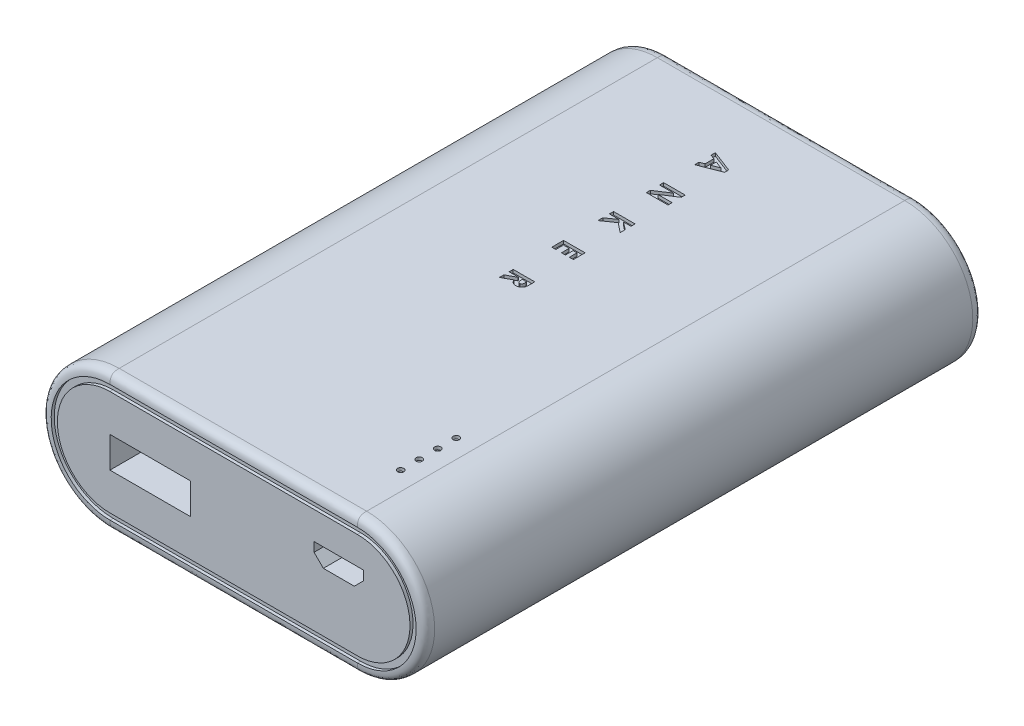
SolidWorks part; units mm, degrees
ref_plane "Front Plane" through (0, 0, 0) normal (0, 0, 1) x (1, 0, 0)
ref_plane "Top Plane" through (0, 0, 0) normal (0, 1, 0) x (1, 0, 0)
ref_plane "Right Plane" through (0, 0, 0) normal (1, 0, 0) x (0, 0, -1)
sketch "Sketch1" plane through (0, 0, 0) normal (0, 0, 1) x (1, 0, 0)
  line L0 (-34.7795, 0) -> (27.2205, 0) construction
  line L1 (-3.7795, 11) -> (-3.7795, -11) construction
  line L2 (-23.7795, 11) -> (16.2205, 11)
  line L3 (-23.7795, -11) -> (16.2205, -11)
  circle A0 centre (-23.7795, 0) radius 11 construction
  circle A1 centre (16.2205, 0) radius 11 construction
  arc A2 (-23.7795, 11) -> (-23.7795, -11) centre (-23.7795, 0) ccw
  arc A3 (16.2205, -11) -> (16.2205, 11) centre (16.2205, 0) ccw
  dimension "D3" = 22
  dimension "D4" = 22
  dimension "D1" = 62
  dimension "D2" = 22
  dimension "D5" = 20
extrude "Boss-Extrude2" add sketch "Sketch1" along normal blind 90 contours L2 A3 L3 A2
sketch "Sketch2" plane through (0, 0, 90) normal (0, 0, 1) x (1, 0, 0)
  line L1 (-23.7795, 2.5) -> (-10.7795, 2.5)
  line L2 (-23.7795, 2.5) -> (-23.7795, -2.5)
  line L3 (-23.7795, -2.5) -> (-10.7795, -2.5)
  line L4 (-10.7795, 2.5) -> (-10.7795, -2.5)
  dimension "D1" = 13
  dimension "D2" = 5
  dimension "D3" = 2.5
  dimension "D4" = 11
extrude "Cut-Extrude1" cut sketch "Sketch2" against normal blind 10
sketch "Sketch3" plane through (0, 0, 90) normal (0, 0, 1) x (1, 0, 0)
  line L0 (9.2205, 4) -> (17.2205, 4)
  line L1 (17.2205, 4) -> (17.2205, 2.5)
  line L2 (17.2205, 2.5) -> (15.7205, 1)
  line L3 (15.7205, 1) -> (10.7205, 1)
  line L4 (10.7205, 1) -> (9.2205, 2.5)
  line L5 (9.2205, 2.5) -> (9.2205, 4)
  point P2 (15.1383, 1.0626)
  point P7 (0, 0)
  dimension "D1" = 8
  dimension "D2" = 5
  dimension "D3" = 3
  dimension "D4" = 1.5
  dimension "D5" = 1.5
  dimension "D6" = 1
  dimension "D7" = 10
extrude "Cut-Extrude2" cut sketch "Sketch3" against normal blind 5
fillet "Fillet1" radius 1.5 4 edges at (-34.7795, 0, 90) (-3.7795, -11, 90) (27.2205, 0, 90) (-3.7795, 11, 90) curvature continuous yes
sketch "Sketch4" plane through (0, 0, 90) normal (0, 0, 1) x (1, 0, 0)
  line L4 (-23.7795, -8.5) -> (16.2205, -8.5)
  line L5 (16.2205, 8.5) -> (-23.7795, 8.5)
  line L6 (-23.7795, -8.5) -> (16.2205, -8.5)
  line L7 (16.2205, 8.5) -> (-23.7795, 8.5)
  line L12 (-23.7795, -9.5) -> (16.2205, -9.5)
  line L13 (16.2205, 9.5) -> (-23.7795, 9.5)
  line L14 (-23.7795, -9.5) -> (16.2205, -9.5)
  line L15 (16.2205, 9.5) -> (-23.7795, 9.5)
  spline S4 degree 3 poles (343.2267, -3971.8149) (-612.7811, 2316.078) (-95.2895, -30.8151) (18.148, -8.285) (18.4171, -8.2175) (18.9506, -8.055) (19.2157, -7.9596) (19.9879, -7.6399) (20.477, -7.3805) (21.4009, -6.764) (21.8375, -6.4036) (22.6224, -5.6191) (22.9758, -5.1922) (23.4421, -4.4952) (23.5867, -4.2533) (23.8484, -3.7618) (23.9665, -3.5108) (24.1787, -2.999) (24.2728, -2.7382) (24.4354, -2.2062) (24.5042, -1.9336) (24.6681, -1.1098) (24.7202, -0.5578) (24.7206, 0.274) (24.7077, 0.5519) (24.6539, 1.1091) (24.613, 1.3872) (24.4501, 2.2051) (24.2878, 2.7344) (23.9688, 3.5059) (23.8491, 3.7606) (23.5866, 4.2537) (23.444, 4.492) (22.9826, 5.1827) (22.6302, 5.6106) (21.8384, 6.4034) (21.4088, 6.7578) (20.719, 7.2194) (20.4812, 7.362) (19.9897, 7.6243) (19.7349, 7.7444) (18.9622, 8.065) (18.4329, 8.2277) (-15.4752, 15.0123) (-115.9896, -182.7222) (3962.0184, -608.1779) knots -12.967802 -12.967802 -12.967802 -12.967802 0.0625 0.0625 0.09375 0.09375 0.125 0.125 0.1875 0.1875 0.25 0.25 0.3125 0.3125 0.34375 0.34375 0.375 0.375 0.40625 0.40625 0.4375 0.4375 0.5 0.5 0.53125 0.53125 0.5625 0.5625 0.625 0.625 0.65625 0.65625 0.6875 0.6875 0.75 0.75 0.8125 0.8125 0.84375 0.84375 0.875 0.875 0.9375 0.9375 4.768553 4.768553 4.768553 4.768553 only from (16.2205, -8.5) to (16.2205, 8.5)
  spline S5 degree 3 poles (-350.7857, 3971.8149) (605.2221, -2316.078) (87.7305, 30.8151) (-25.707, 8.285) (-25.9761, 8.2175) (-26.5096, 8.055) (-26.7747, 7.9596) (-27.5469, 7.6399) (-28.036, 7.3805) (-28.9599, 6.764) (-29.3965, 6.4036) (-30.1814, 5.6191) (-30.5348, 5.1922) (-31.0011, 4.4952) (-31.1457, 4.2533) (-31.4074, 3.7618) (-31.5255, 3.5108) (-31.7377, 2.999) (-31.8318, 2.7382) (-31.9944, 2.2062) (-32.0632, 1.9336) (-32.2271, 1.1098) (-32.2793, 0.5578) (-32.2796, -0.274) (-32.2668, -0.5519) (-32.213, -1.1091) (-32.172, -1.3872) (-32.0091, -2.2051) (-31.8469, -2.7344) (-31.5278, -3.5059) (-31.4081, -3.7606) (-31.1456, -4.2537) (-31.003, -4.492) (-30.5417, -5.1827) (-30.1892, -5.6106) (-29.3975, -6.4034) (-28.9678, -6.7578) (-28.278, -7.2194) (-28.0402, -7.362) (-27.5488, -7.6243) (-27.2939, -7.7444) (-26.5212, -8.065) (-25.9919, -8.2277) (7.9161, -15.0123) (108.4306, 182.7222) (-3969.5774, 608.1779) knots -12.967802 -12.967802 -12.967802 -12.967802 0.0625 0.0625 0.09375 0.09375 0.125 0.125 0.1875 0.1875 0.25 0.25 0.3125 0.3125 0.34375 0.34375 0.375 0.375 0.40625 0.40625 0.4375 0.4375 0.5 0.5 0.53125 0.53125 0.5625 0.5625 0.625 0.625 0.65625 0.65625 0.6875 0.6875 0.75 0.75 0.8125 0.8125 0.84375 0.84375 0.875 0.875 0.9375 0.9375 4.768553 4.768553 4.768553 4.768553 only from (-23.7795, 8.5) to (-23.7795, -8.5)
  spline S6 degree 3 poles (16.2205, -8.5) (16.7817, -8.5) (17.3338, -8.4467) (18.148, -8.285) (18.4171, -8.2175) (18.9506, -8.055) (19.2157, -7.9596) (19.9879, -7.6399) (20.477, -7.3805) (21.4009, -6.764) (21.8375, -6.4036) (22.6224, -5.6191) (22.9758, -5.1922) (23.4421, -4.4952) (23.5867, -4.2533) (23.8484, -3.7618) (23.9665, -3.5108) (24.1787, -2.999) (24.2728, -2.7382) (24.4354, -2.2062) (24.5042, -1.9336) (24.6681, -1.1098) (24.7202, -0.5578) (24.7206, 0.274) (24.7077, 0.5519) (24.6539, 1.1091) (24.613, 1.3872) (24.4501, 2.2051) (24.2878, 2.7344) (23.9688, 3.5059) (23.8491, 3.7606) (23.5866, 4.2537) (23.444, 4.492) (22.9826, 5.1827) (22.6302, 5.6106) (21.8384, 6.4034) (21.4088, 6.7578) (20.719, 7.2194) (20.4812, 7.362) (19.9897, 7.6243) (19.7349, 7.7444) (18.9622, 8.065) (18.4329, 8.2277) (17.3443, 8.4455) (16.7821, 8.5) (16.2205, 8.5) knots 0 0 0 0 0.0625 0.0625 0.09375 0.09375 0.125 0.125 0.1875 0.1875 0.25 0.25 0.3125 0.3125 0.34375 0.34375 0.375 0.375 0.40625 0.40625 0.4375 0.4375 0.5 0.5 0.53125 0.53125 0.5625 0.5625 0.625 0.625 0.65625 0.65625 0.6875 0.6875 0.75 0.75 0.8125 0.8125 0.84375 0.84375 0.875 0.875 0.9375 0.9375 1 1 1 1
  spline S7 degree 3 poles (-23.7795, 8.5) (-24.3407, 8.5) (-24.8928, 8.4467) (-25.707, 8.285) (-25.9761, 8.2175) (-26.5096, 8.055) (-26.7747, 7.9596) (-27.5469, 7.6399) (-28.036, 7.3805) (-28.9599, 6.764) (-29.3965, 6.4036) (-30.1814, 5.6191) (-30.5348, 5.1922) (-31.0011, 4.4952) (-31.1457, 4.2533) (-31.4074, 3.7618) (-31.5255, 3.5108) (-31.7377, 2.999) (-31.8318, 2.7382) (-31.9944, 2.2062) (-32.0632, 1.9336) (-32.2271, 1.1098) (-32.2793, 0.5578) (-32.2796, -0.274) (-32.2668, -0.5519) (-32.213, -1.1091) (-32.172, -1.3872) (-32.0091, -2.2051) (-31.8469, -2.7344) (-31.5278, -3.5059) (-31.4081, -3.7606) (-31.1456, -4.2537) (-31.003, -4.492) (-30.5417, -5.1827) (-30.1892, -5.6106) (-29.3975, -6.4034) (-28.9678, -6.7578) (-28.278, -7.2194) (-28.0402, -7.362) (-27.5488, -7.6243) (-27.2939, -7.7444) (-26.5212, -8.065) (-25.9919, -8.2277) (-24.9033, -8.4455) (-24.3411, -8.5) (-23.7795, -8.5) knots 0 0 0 0 0.0625 0.0625 0.09375 0.09375 0.125 0.125 0.1875 0.1875 0.25 0.25 0.3125 0.3125 0.34375 0.34375 0.375 0.375 0.40625 0.40625 0.4375 0.4375 0.5 0.5 0.53125 0.53125 0.5625 0.5625 0.625 0.625 0.65625 0.65625 0.6875 0.6875 0.75 0.75 0.8125 0.8125 0.84375 0.84375 0.875 0.875 0.9375 0.9375 1 1 1 1
  spline S10 degree 2 poles (-1024.0256, 3849.5599) (-109.4484, -62.3267) (19.856, -8.7769) (21.6012, -8.0541) (22.938, -6.7175) (24.2738, -5.382) (24.9973, -3.6355) (25.7203, -1.8904) (25.7205, 0) (25.7206, 1.8889) (24.9973, 3.6355) (24.2746, 5.3807) (22.938, 6.7175) (21.6025, 8.0533) (19.856, 8.7769) (-109.3542, 62.3114) (-1031.8812, -3847.3339) knots -9.131418 -9.131418 -9.131418 0.125 0.125 0.25 0.25 0.375 0.375 0.5 0.5 0.625 0.625 0.75 0.75 0.875 0.875 10.128784 10.128784 10.128784 only from (16.2205, -9.5) to (16.2205, 9.5)
  spline S11 degree 2 poles (1016.4666, -3849.5599) (101.8893, 62.3267) (-27.415, 8.7769) (-29.1602, 8.0541) (-30.497, 6.7175) (-31.8328, 5.382) (-32.5564, 3.6355) (-33.2794, 1.8904) (-33.2795, 0) (-33.2797, -1.8889) (-32.5564, -3.6355) (-31.8336, -5.3807) (-30.497, -6.7175) (-29.1615, -8.0533) (-27.415, -8.7769) (101.7952, -62.3114) (1024.3222, 3847.3339) knots -9.131418 -9.131418 -9.131418 0.125 0.125 0.25 0.25 0.375 0.375 0.5 0.5 0.625 0.625 0.75 0.75 0.875 0.875 10.128784 10.128784 10.128784 only from (-23.7795, 9.5) to (-23.7795, -9.5)
  spline S12 degree 2 poles (16.2205, -9.5) (18.1098, -9.5) (19.856, -8.7769) (21.6012, -8.0541) (22.938, -6.7175) (24.2738, -5.382) (24.9973, -3.6355) (25.7203, -1.8904) (25.7205, 0) (25.7206, 1.8889) (24.9973, 3.6355) (24.2746, 5.3807) (22.938, 6.7175) (21.6025, 8.0533) (19.856, 8.7769) (18.1106, 9.5) (16.2205, 9.5) knots 0 0 0 0.125 0.125 0.25 0.25 0.375 0.375 0.5 0.5 0.625 0.625 0.75 0.75 0.875 0.875 1 1 1
  spline S13 degree 2 poles (-23.7795, 9.5) (-25.6689, 9.5) (-27.415, 8.7769) (-29.1602, 8.0541) (-30.497, 6.7175) (-31.8328, 5.382) (-32.5564, 3.6355) (-33.2794, 1.8904) (-33.2795, 0) (-33.2797, -1.8889) (-32.5564, -3.6355) (-31.8336, -5.3807) (-30.497, -6.7175) (-29.1615, -8.0533) (-27.415, -8.7769) (-25.6696, -9.5) (-23.7795, -9.5) knots 0 0 0 0.125 0.125 0.25 0.25 0.375 0.375 0.5 0.5 0.625 0.625 0.75 0.75 0.875 0.875 1 1 1
  dimension "D1" = 1
  dimension "D2" = 0
extrude "Cut-Extrude3" cut sketch "Sketch4" against normal blind 0.5
fillet "Fillet2" radius 1.5 4 edges at (-34.7795, 0, 0) (-3.7795, -11, 0) (27.2205, 0, 0) (-3.7795, 11, 0) curvature continuous yes
sketch "Sketch5" plane through (0, 0, 0) normal (0, 0, -1) x (-1, 0, 0)
  line L2 (23.7795, 8.5) -> (-16.2205, 8.5)
  line L3 (-16.2205, -8.5) -> (23.7795, -8.5)
  line L4 (-16.2205, -9.5) -> (23.7795, -9.5)
  line L5 (23.7795, 9.5) -> (-16.2205, 9.5)
  line L6 (-16.2205, -9.5) -> (23.7795, -9.5)
  line L7 (23.7795, 9.5) -> (-16.2205, 9.5)
  spline S2 degree 1 poles (-16.2205, 8.5) (-16.2205, -8.5) knots 0 0 1 1 construction
  spline S3 degree 1 poles (23.7795, -8.5) (23.7795, 8.5) knots 0 0 1 1 construction
  spline S4 degree 2 poles (-786.4293, 2876.4255) (-84.64, -55.183) (27.415, -8.7769) (29.1602, -8.0541) (30.497, -6.7175) (31.8328, -5.382) (32.5564, -3.6355) (33.2794, -1.8904) (33.2795, 0) (33.2797, 1.8889) (32.5564, 3.6355) (31.8336, 5.3807) (30.497, 6.7175) (29.1615, 8.0533) (27.415, 8.7769) (-84.5575, 55.1695) (-792.2955, -2874.7097) knots -7.896598 -7.896598 -7.896598 0.125 0.125 0.25 0.25 0.375 0.375 0.5 0.5 0.625 0.625 0.75 0.75 0.875 0.875 8.894251 8.894251 8.894251 only from (23.7795, -9.5) to (23.7795, 9.5)
  spline S5 degree 2 poles (793.9883, -2876.4255) (92.199, 55.183) (-19.856, 8.7769) (-21.6012, 8.0541) (-22.938, 6.7175) (-24.2738, 5.382) (-24.9973, 3.6355) (-25.7203, 1.8904) (-25.7205, 0) (-25.7206, -1.8889) (-24.9973, -3.6355) (-24.2746, -5.3807) (-22.938, -6.7175) (-21.6025, -8.0533) (-19.856, -8.7769) (92.1165, -55.1695) (799.8546, 2874.7097) knots -7.896598 -7.896598 -7.896598 0.125 0.125 0.25 0.25 0.375 0.375 0.5 0.5 0.625 0.625 0.75 0.75 0.875 0.875 8.894251 8.894251 8.894251 only from (-16.2205, 9.5) to (-16.2205, -9.5)
  spline S6 degree 2 poles (23.7795, -9.5) (25.6689, -9.5) (27.415, -8.7769) (29.1602, -8.0541) (30.497, -6.7175) (31.8328, -5.382) (32.5564, -3.6355) (33.2794, -1.8904) (33.2795, 0) (33.2797, 1.8889) (32.5564, 3.6355) (31.8336, 5.3807) (30.497, 6.7175) (29.1615, 8.0533) (27.415, 8.7769) (25.6696, 9.5) (23.7795, 9.5) knots 0 0 0 0.125 0.125 0.25 0.25 0.375 0.375 0.5 0.5 0.625 0.625 0.75 0.75 0.875 0.875 1 1 1
  spline S7 degree 2 poles (-16.2205, 9.5) (-18.1098, 9.5) (-19.856, 8.7769) (-21.6012, 8.0541) (-22.938, 6.7175) (-24.2738, 5.382) (-24.9973, 3.6355) (-25.7203, 1.8904) (-25.7205, 0) (-25.7206, -1.8889) (-24.9973, -3.6355) (-24.2746, -5.3807) (-22.938, -6.7175) (-21.6025, -8.0533) (-19.856, -8.7769) (-18.1106, -9.5) (-16.2205, -9.5) knots 0 0 0 0.125 0.125 0.25 0.25 0.375 0.375 0.5 0.5 0.625 0.625 0.75 0.75 0.875 0.875 1 1 1
  spline S8 degree 2 poles (-16.2205, 8.5) (-17.4846, 8.5016) (-19.8912, 7.7681) (-22.3469, 6.1274) (-24.226, 3.3158) (-24.8853, -0.0001) (-24.2259, -3.3159) (-22.3468, -6.1275) (-19.8908, -7.7681) (-17.4853, -8.5016) (-16.2205, -8.5) knots 0 0 0 0.09375 0.1875 0.3125 0.4375 0.5625 0.6875 0.8125 0.90625 1 1 1
  spline S9 degree 2 poles (23.7795, -8.5) (25.0436, -8.5016) (27.4502, -7.7681) (29.9059, -6.1274) (31.785, -3.3158) (32.4444, 0.0001) (31.7849, 3.3159) (29.9058, 6.1275) (27.4498, 7.7681) (25.0443, 8.5016) (23.7795, 8.5) knots 0 0 0 0.09375 0.1875 0.3125 0.4375 0.5625 0.6875 0.8125 0.90625 1 1 1
  dimension "D1" = 0
  dimension "D2" = 1
extrude "Cut-Extrude4" cut sketch "Sketch5" against normal blind 0.5
sketch "Sketch9" plane through (0, 11, 0) normal (0, 1, 0) x (1, 0, 0)
  line L0 (-23.7795, 0) -> (16.2205, 0) construction
  line L1 (-34.7795, -1.5) -> (-34.7795, -88.5) construction
  text T0 "<b><r-90>A</b>\r\n<b><r-90>N</b>\r\n<b><r-90>K</b>\r\n<b><r-90>E</b>\r\n<b><r-90>R</b>" font "Century Gothic" height 3.5
  dimension "D1" = 10
  dimension "D2" = 29
extrude "Cut-Extrude5" cut sketch "Sketch9" against normal blind 0.5
sketch "Sketch10" plane through (0, 11, 0) normal (0, 1, 0) x (1, 0, 0)
  line L0 (16.2205, -90) -> (-23.7795, -90) construction
  line L1 (27.2205, -88.5) -> (27.2205, -1.5) construction
  circle A0 centre (13.2205, -71) radius 0.5
  circle A1 centre (13.2205, -74) radius 0.5
  circle A2 centre (13.2205, -77) radius 0.5
  circle A3 centre (13.2205, -80) radius 0.5
  point P8 (0, 0)
  point P9 (0, 0)
  point P10 (0, 0)
  point P11 (0, 0)
  point P12 (0, 0)
  point P17 (0, 0)
  dimension "D1" = 1
  dimension "D2" = 1
  dimension "D3" = 1
  dimension "D4" = 1
  dimension "D5" = 3
  dimension "D6" = 3
  dimension "D7" = 3
  dimension "D8" = 10
  dimension "D9" = 14
extrude "Cut-Extrude6" cut sketch "Sketch10" against normal blind 0.5
